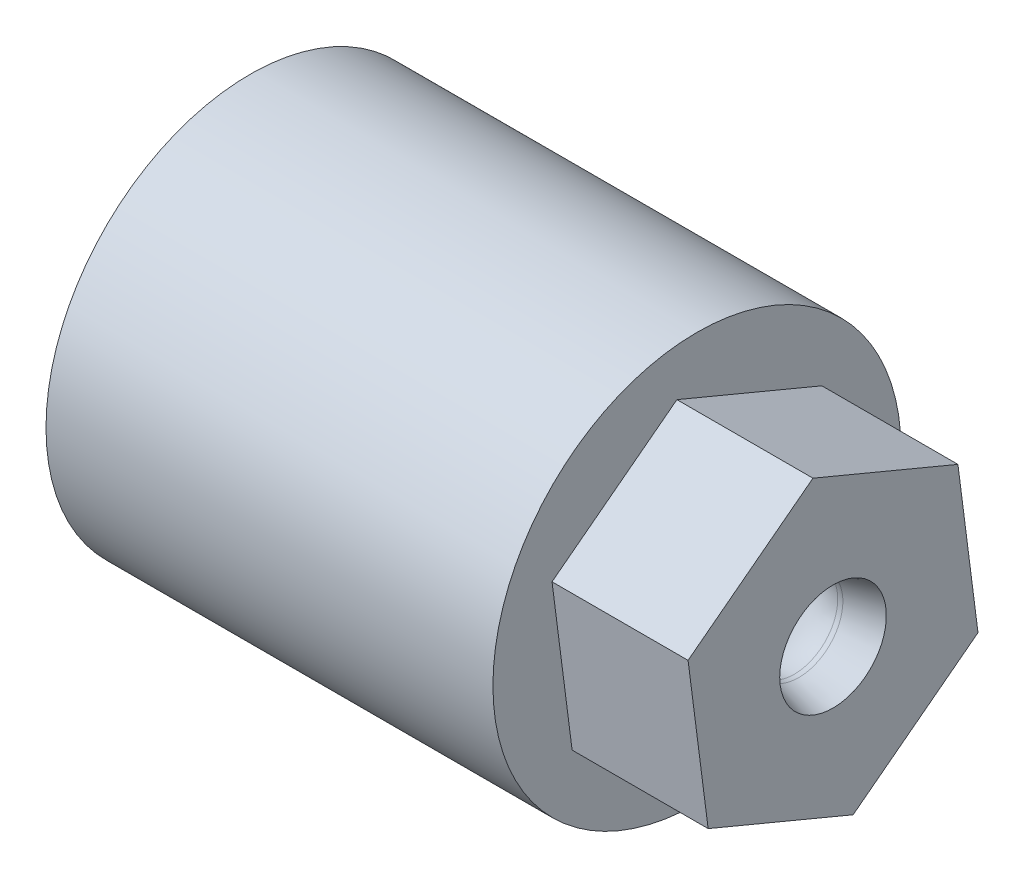
SolidWorks part; units mm, degrees
ref_plane "Front Plane" through (0, 0, 0) normal (0, 0, 1) x (1, 0, 0)
ref_plane "Top Plane" through (0, 0, 0) normal (0, 1, 0) x (1, 0, 0)
ref_plane "Right Plane" through (0, 0, 0) normal (1, 0, 0) x (0, 0, -1)
sketch "Sketch1" plane through (0, 0, 0) normal (0, 0, 1) x (1, 0, 0)
  line L0 (0, 0) -> (1.8114, 0) construction
  line L1 (0.2104, 2.0597) -> (1.8114, 2.4887)
  line L2 (-2.1553, 2.9247) -> (-4.048, 4.8174)
  line L3 (-25.4, 5.7474) -> (-25.4, 9.525)
  line L4 (-6.293, 5.7474) -> (-25.4, 5.7474)
  line L5 (-25.4, 9.525) -> (-10.8886, 9.525)
  line L6 (1.8114, 9.525) -> (1.8114, 2.4887)
  line L8 (-10.8886, 9.525) -> (1.8114, 9.525)
  arc A0 (-2.1553, 2.9247) -> (0, 2.032) centre (0, 5.08) ccw
  arc A1 (0, 2.032) -> (0.2104, 2.0597) centre (0, 2.8448) ccw
  arc A2 (-4.048, 4.8174) -> (-6.293, 5.7474) centre (-6.293, 2.5724) ccw
  dimension "D3" = 3.048
  dimension "D4" = 0.8128
  dimension "D11" = 3.175
  dimension "D1" = 2.032
  dimension "D2" = 1.8114
  dimension "D5" = 2.4887
  dimension "D6" = 15
  dimension "D7" = 45
  dimension "D8" = 5.7474
  dimension "D9" = 25.4
  dimension "D10" = 9.525
  dimension "D13" = 12.7
revolve "Revolve1" add sketch "Sketch1" angle 360 about L0
sketch "Sketch3" plane through (1.8114, 0, 0) normal (1, 0, 0) x (0, 0, -1)
  line L1 (0.9374, -7.2722) -> (6.7666, -2.8242)
  line L2 (6.7666, -2.8242) -> (5.8292, 4.4479)
  line L3 (5.8292, 4.4479) -> (-0.9374, 7.2722)
  line L4 (-0.9374, 7.2722) -> (-6.7666, 2.8242)
  line L5 (-6.7666, 2.8242) -> (-5.8292, -4.4479)
  line L6 (-5.8292, -4.4479) -> (0.9374, -7.2722)
  circle A0 centre (0, 0) radius 6.35 construction
  circle M7 centre (0, 0) radius 9.525
  dimension "D1" = 12.7
extrude "Cut-Extrude2" cut sketch "Sketch3" against normal blind 6.35 contours L6 L5 L4 L3 L2 L1 M7 region at (1.8114, 0, 9.2556)
equation "\"D3@Sketch1\"= 1.5 * \"D1@Sketch1\""
equation "\"D4@Sketch1\"=.4 * \"D1@Sketch1\""
equation "\"D5@Sketch1\"=\"D1@Sketch1\" * ( 1.5 ) ^ .5"
equation "\"D8@Sketch1\"=\"D1@Sketch1\" * ( 8 ) ^ .5"
equation "\"er\"= 4"
